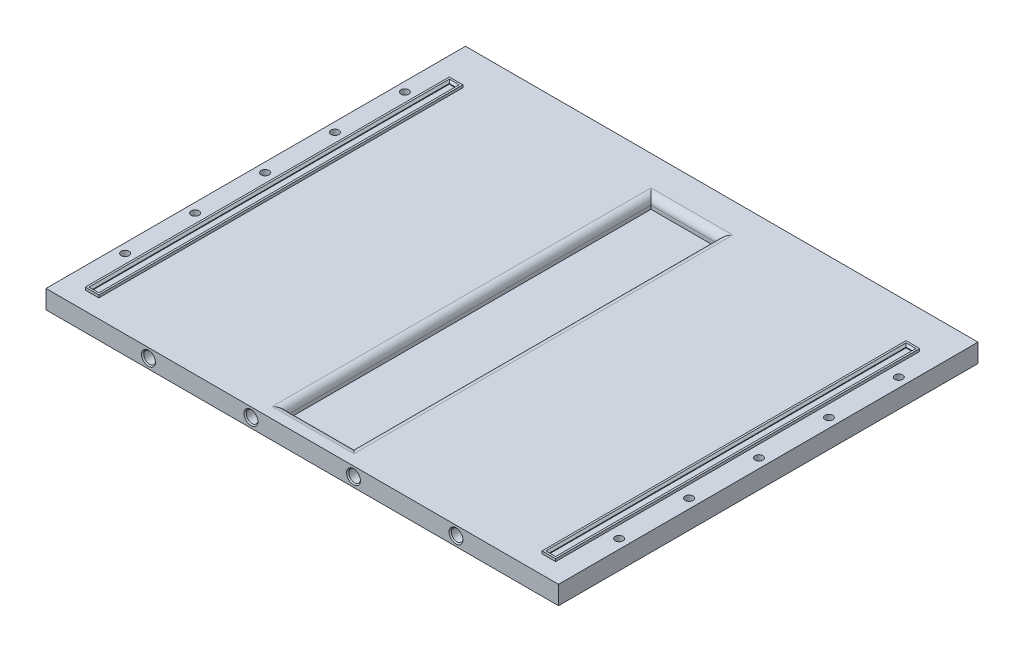
SolidWorks part; units mm, degrees
ref_plane "Спереди" through (0, 0, 0) normal (0, 0, 1) x (1, 0, 0)
ref_plane "Сверху" through (0, 0, 0) normal (0, 1, 0) x (1, 0, 0)
ref_plane "Справа" through (0, 0, 0) normal (1, 0, 0) x (0, 0, -1)
sketch "Эскиз1" plane through (0, 0, 0) normal (0, 1, 0) x (1, 0, 0)
  line L5 (-69.03, -56.5) -> (69.03, -56.5)
  line L6 (-69.03, -56.5) -> (-69.03, 56.5)
  line L7 (-69.03, 56.5) -> (69.03, 56.5)
  line L8 (69.03, -56.5) -> (69.03, 56.5)
  line L9 (-69.03, -56.5) -> (69.03, 56.5) construction
  line L10 (-69.03, 56.5) -> (69.03, -56.5) construction
  point P0 (0, 0)
  dimension "D1" = 113
  dimension "D2" = 138.06
extrude "Основание" add sketch "Эскиз1" along normal blind 5
sketch "Эскиз6" plane through (0, 0, 0) normal (0, -1, 0) x (1, 0, 0)
  line L0 (0, 45.5668) -> (0, -26.923) construction
  line L1 (-15.8226, 0) -> (3.0664, 0) construction
  line L2 (-37, 37) -> (0, 37) construction
  line L3 (-47, 47) -> (-27, 47)
  line L4 (-47, 47) -> (-47, 27)
  line L5 (-47, 27) -> (-27, 27)
  line L6 (-27, 47) -> (-27, 27)
  line L7 (-47, 47) -> (-27, 27) construction
  line L8 (-47, 27) -> (-27, 47) construction
  line L9 (-37, 37) -> (-37, 0) construction
  line L10 (47, 47) -> (27, 47)
  line L11 (47, 47) -> (47, 27)
  line L12 (47, 27) -> (27, 27)
  line L13 (27, 47) -> (27, 27)
  line L14 (27, -47) -> (27, -27)
  line L15 (47, -27) -> (27, -27)
  line L16 (47, -47) -> (47, -27)
  line L17 (47, -47) -> (27, -47)
  line L18 (-47, -47) -> (-27, -47)
  line L19 (-47, -47) -> (-47, -27)
  line L20 (-47, -27) -> (-27, -27)
  line L21 (-27, -47) -> (-27, -27)
  point P1 (-37, 37)
  dimension "D1" = 20
  dimension "D2" = 37
extrude "Ножки" add sketch "Эскиз6" along normal blind 4
fillet "Скругление ножек" radius 2 16 edges at (-37, -4, 27) (-47, -4, 37) (-37, -4, 47) (-27, -4, 37) (-37, -4, -27) (-27, -4, -37) (-37, -4, -47) (-47, -4, -37) (27, -4, -37) (37, -4, -27) (47, -4, -37) (37, -4, -47) (37, -4, 27) (27, -4, 37) (37, -4, 47) (47, -4, 37)
fillet "Скругление3" radius 2 48 edges at (46.4142, -3.4142, 27.5858) (27.5858, -3.4142, 27.5858) (46.4142, -3.4142, 46.4142) (27.5858, -3.4142, 46.4142) (-46.4142, -3.4142, 46.4142) (27.5858, -3.4142, -27.5858) (-46.4142, -3.4142, 27.5858) (-27.5858, -3.4142, 27.5858) (-27.5858, -3.4142, 46.4142) (27.5858, -3.4142, -46.4142) (46.4142, -3.4142, -46.4142) (46.4142, -3.4142, -27.5858) (-27.5858, -3.4142, -46.4142) (-46.4142, -3.4142, -46.4142) (-27.5858, -3.4142, -27.5858) (-46.4142, -3.4142, -27.5858) (37, 0, 27) (47, 0, 37) (47, -1, 27) (27, 0, 37) (27, -1, 27) (37, 0, 47) (47, -1, 47) (27, -1, 47) (-47, 0, 37) (-37, 0, 47) (-47, -1, 47) (27, 0, -37) (37, 0, -27) (27, -1, -27) (-37, 0, 27) (-47, -1, 27) (-27, 0, 37) (-27, -1, 27) (-27, -1, 47) (37, 0, -47) (27, -1, -47) (47, 0, -37) (47, -1, -47) (47, -1, -27) (-37, 0, -47) (-27, 0, -37) (-27, -1, -47) (-47, 0, -37) (-47, -1, -47) (-37, 0, -27) (-27, -1, -27) (-47, -1, -27)
sketch "Эскиз2" plane through (0, 5, 0) normal (0, 1, 0) x (1, 0, 0)
  line L0 (0, 0) -> (0, -25.5598) construction
  line L1 (-61.525, 37.0772) -> (-61.525, 5.6487) construction
  line L2 (-21.6597, -2.575) -> (12.5108, -2.575) construction
  line L3 (-59.7, 46.45) -> (-63.35, 46.45)
  line L4 (-63.35, 46.45) -> (-63.35, -51.6)
  line L5 (-63.35, -2.575) -> (-62.35, -2.575)
  line L6 (-62.35, -50.6) -> (-62.35, 45.45)
  line L7 (-62.35, 45.45) -> (-60.7, 45.45)
  line L8 (-61.525, 45.45) -> (-61.525, 46.45)
  line L9 (-60.7, -50.6) -> (-60.7, 45.45)
  line L10 (-59.7, -2.575) -> (-60.7, -2.575)
  line L11 (-59.7, 46.45) -> (-59.7, -51.6)
  line L12 (-62.35, -50.6) -> (-60.7, -50.6)
  line L13 (-59.7, -51.6) -> (-63.35, -51.6)
  line L14 (-61.525, -50.6) -> (-61.525, -51.6)
  line L15 (61.525, -50.6) -> (61.525, -51.6)
  line L16 (59.7, -51.6) -> (63.35, -51.6)
  line L17 (62.35, -50.6) -> (60.7, -50.6)
  line L18 (59.7, 46.45) -> (59.7, -51.6)
  line L19 (59.7, -2.575) -> (60.7, -2.575)
  line L20 (60.7, -50.6) -> (60.7, 45.45)
  line L21 (61.525, 45.45) -> (61.525, 46.45)
  line L22 (62.35, 45.45) -> (60.7, 45.45)
  line L23 (62.35, -50.6) -> (62.35, 45.45)
  line L24 (63.35, -2.575) -> (62.35, -2.575)
  line L25 (63.35, 46.45) -> (63.35, -51.6)
  line L26 (59.7, 46.45) -> (63.35, 46.45)
  line L27 (-69.03, -56.5) -> (69.03, -56.5) construction
  dimension "D1" = 1
  dimension "D2" = 96.05
  dimension "D3" = 1.65
  dimension "D4" = 121.4
  dimension "D5" = 5.9
extrude "Ложемент материнской платы" add sketch "Эскиз2" along normal blind 0.7 contours L14 L12 L6 L5 L4 L13 | L7 L8 L3 L4 L5 L6 | L11 L3 L8 L7 L9 L10 | L12 L14 L13 L11 L10 L9 | L26 L21 L22 L23 L24 L25 | L26 L18 L19 L20 L22 L21 | L17 L20 L19 L18 L16 L15 | L25 L24 L23 L17 L15 L16 region at (-60.2151, 5, -22.3349) region at (-62.8349, 5, -22.3349) region at (-60.2151, 5, 27.4849) region at (-62.8349, 5, 27.4849) region at (62.8349, 5, 27.4849) region at (60.2151, 5, 27.4849) region at (62.8349, 5, -22.3349) region at (60.2151, 5, -22.3349)
fillet "Фаска первого ложемента" radius 0.5 4 edges at (-61.525, 5.7, -45.45) (-60.7, 5.7, 2.575) (-61.525, 5.7, 50.6) (-62.35, 5.7, 2.575) type face fillet profile chamfer first side face at (-61.525, 5.35, -45.45) first side face at (-61.525, 5.35, 50.6) first side face at (-60.7, 5.35, 2.575) first side face at (-62.35, 5.35, 2.575) second side face at (-61.525, 5.7, 2.575)
fillet "Фаска второго ложемента" radius 0.5 4 edges at (61.525, 5.7, 50.6) (60.7, 5.7, 2.575) (61.525, 5.7, -45.45) (62.35, 5.7, 2.575) type face fillet profile chamfer first side face at (61.525, 5.35, -45.45) first side face at (62.35, 5.35, 2.575) first side face at (60.7, 5.35, 2.575) first side face at (61.525, 5.35, 50.6) second side face at (61.525, 5.7, 2.575)
sketch "Эскиз3" plane through (0, 0, -56.5) normal (0, 0, -1) x (-1, 0, 0)
  line L0 (-69.03, 0) -> (69.03, 0) construction
  line L1 (-69.03, 5) -> (-69.03, 0) construction
  line L2 (-41.418, 2.5) -> (-69.03, 2.5) construction
  line L3 (41.418, 2.5) -> (69.03, 2.5) construction
  line L6 (69.03, 5) -> (69.03, 0) construction
  line L7 (-41.418, 2.5) -> (-13.806, 2.5) construction
  line L8 (-13.806, 2.5) -> (13.806, 2.5) construction
  line L9 (13.806, 2.5) -> (41.418, 2.5) construction
  circle A0 centre (-41.418, 2.5) radius 1.575
  circle A1 centre (-13.806, 2.5) radius 1.575
  circle A2 centre (13.806, 2.5) radius 1.575
  circle A3 centre (41.418, 2.5) radius 1.575
  dimension "D4" = 3.15
  dimension "D1" = 2.5
  dimension "D5" = 27.612
  dimension "D3" = 4
extrude "Крепежные отверсия передней и задней стенки" cut sketch "Эскиз3" against normal blind 4.2
ref_plane "Плоскость1" through (0, 0, 0) normal (0, 0, -1) x (-1, 0, 0)
mirror "Зеркальное отражение1" about plane through (0, 0, 0) normal (0, 0, -1) of "Крепежные отверсия передней и задней стенки"
chamfer "Фаска под запресовку" distance 0.3 angle 45 8 edges at (39.843, 2.5, -56.5) (-42.993, 2.5, -56.5) (-15.381, 2.5, -56.5) (12.231, 2.5, -56.5) (39.843, 2.5, 56.5) (12.231, 2.5, 56.5) (-15.381, 2.5, 56.5) (-42.993, 2.5, 56.5)
sketch "Эскиз4" plane through (0, 0, 0) normal (0, -1, 0) x (1, 0, 0)
  line L0 (0, 34.8353) -> (0, -23.754) construction
  line L1 (-66.53, 56.5) -> (-66.53, 37.6667) construction
  line L2 (-69.03, 56.5) -> (69.03, 56.5) construction
  line L3 (-66.53, 37.6667) -> (-66.53, 18.8333) construction
  line L4 (-66.53, 18.8333) -> (-66.53, 0) construction
  line L5 (-66.53, 0) -> (-66.53, -18.8333) construction
  line L6 (-66.53, -18.8333) -> (-66.53, -37.6667) construction
  line L7 (-66.53, -37.6667) -> (-66.53, -56.5) construction
  line L8 (69.03, -56.5) -> (-69.03, -56.5) construction
  line L9 (-69.03, -56.5) -> (-69.03, 56.5) construction
  circle A0 centre (-66.53, 37.6667) radius 1.05
  circle A1 centre (-66.53, 18.8333) radius 1.05
  circle A2 centre (-66.53, 0) radius 1.05
  circle A3 centre (-66.53, -18.8333) radius 1.05
  circle A4 centre (-66.53, -37.6667) radius 1.05
  circle A5 centre (66.53, -37.6667) radius 1.05
  circle A6 centre (66.53, -18.8333) radius 1.05
  circle A7 centre (66.53, 0) radius 1.05
  circle A8 centre (66.53, 18.8333) radius 1.05
  circle A9 centre (66.53, 37.6667) radius 1.05
  dimension "D3" = 2.1
  dimension "D2" = 2.5
  dimension "D1" = 5
extrude "Отверстия крепежных винтов" cut sketch "Эскиз4" against normal up to next
sketch "Эскиз5" plane through (0, 0, 0) normal (0, -1, 0) x (1, 0, 0)
  line L0 (0, 88.0608) -> (0, 29.4715) construction
  line L1 (-66.53, 56.5) -> (-66.53, 37.6667) construction
  line L2 (-66.53, 37.6667) -> (-66.53, 18.8333) construction
  line L3 (-66.53, 18.8333) -> (-66.53, 0) construction
  line L4 (-66.53, 0) -> (-66.53, -18.8333) construction
  line L5 (-66.53, -18.8333) -> (-66.53, -37.6667) construction
  line L6 (-66.53, -37.6667) -> (-66.53, -56.5) construction
  line L7 (69.03, -56.5) -> (-69.03, -56.5) construction
  line L8 (-69.03, 56.5) -> (69.03, 56.5) construction
  circle A0 centre (-66.53, 37.6667) radius 2
  circle A1 centre (-66.53, 18.8333) radius 2
  circle A2 centre (-66.53, 0) radius 2
  circle A3 centre (-66.53, -18.8333) radius 2
  circle A4 centre (-66.53, -37.6667) radius 2
  circle A5 centre (66.53, -37.6667) radius 2
  circle A6 centre (66.53, -18.8333) radius 2
  circle A7 centre (66.53, 0) radius 2
  circle A8 centre (66.53, 18.8333) radius 2
  circle A9 centre (66.53, 37.6667) radius 2
  circle A10 centre (-66.53, -37.6667) radius 1.05 construction
  dimension "D1" = 4
extrude "Потай головок винтов" cut sketch "Эскиз5" against normal blind 3
sketch "Эскиз8" plane through (0, 5, 0) normal (0, 1, 0) x (1, 0, 0)
  line L0 (-59.7, 46.45) -> (-38.3699, 46.45) construction
  line L1 (-59.7, -51.6) -> (-44.5392, -51.6) construction
  line L2 (-59.7, -51.6) -> (-63.35, -51.6) construction
  line L3 (-59.7, 46.45) -> (-63.35, 46.45) construction
  line L4 (0, 67.288) -> (0, -49932.712) construction
  line L5 (-9, 46.45) -> (9, 46.45)
  line L6 (-9, 46.45) -> (-9, -51.6)
  line L7 (-9, -51.6) -> (9, -51.6)
  line L8 (9, 46.45) -> (9, -51.6)
  point P16 (0, 46.45)
  dimension "D1" = 18
extrude "Ложемент для кабелей" cut sketch "Эскиз8" against normal blind 3
fillet "Скругление ложемента кабелей" radius 2 4 edges at (-9, 5, 2.575) (0, 5, -46.45) (9, 5, 2.575) (0, 5, 51.6)
